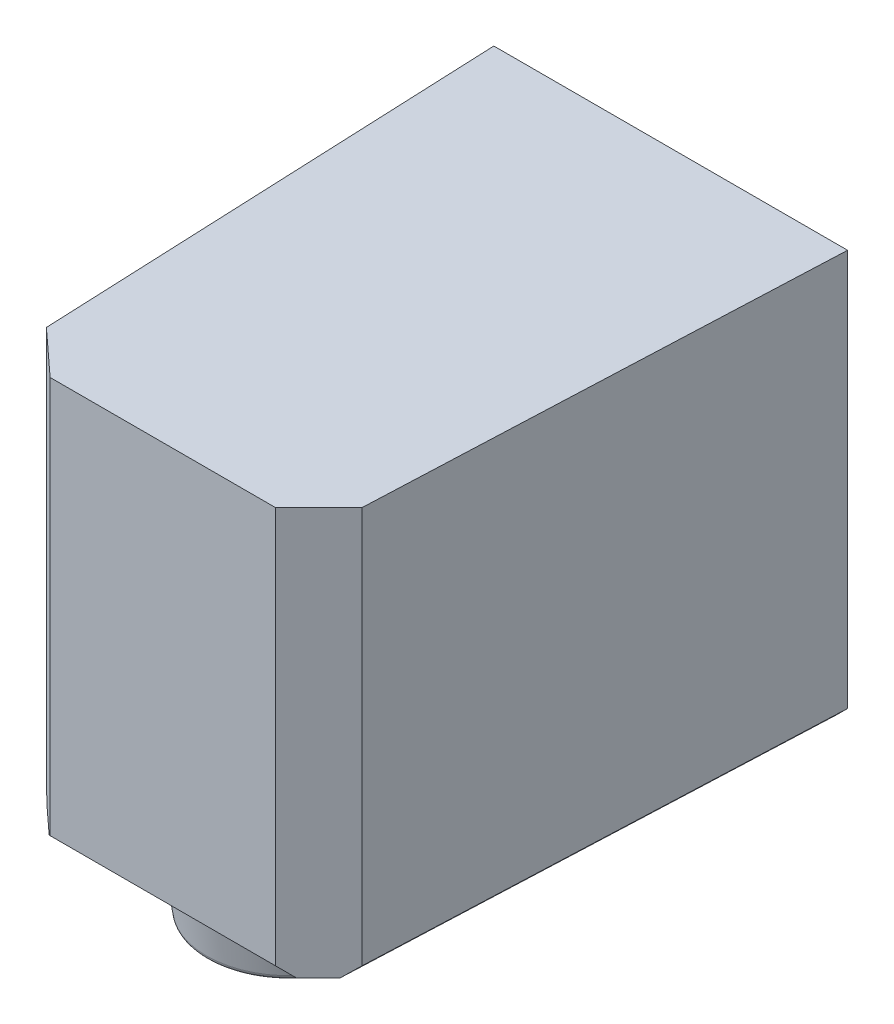
SolidWorks part; units mm, degrees
ref_plane "Front" through (0, 0, 0) normal (0, 0, 1) x (1, 0, 0)
ref_plane "Top" through (0, 0, 0) normal (0, 1, 0) x (1, 0, 0)
ref_plane "Right" through (0, 0, 0) normal (1, 0, 0) x (0, 0, -1)
sketch "Sketch1" plane through (0, 0, 0) normal (0, 1, 0) x (1, 0, 0)
  line L0 (0, 0) -> (68.2, 0)
  line L1 (68.2, 0) -> (64, -98.1)
  line L2 (64, -98.1) -> (4.2, -98.1)
  line L3 (4.2, -98.1) -> (0, 0)
  line L4 (68.2, 0) -> (68.2, -98.1) construction
  line L5 (68.2, -98.1) -> (64, -98.1) construction
  line L6 (0, 0) -> (0, -98.1) construction
  line L7 (0, -98.1) -> (4.2, -98.1) construction
  dimension "D1" = 68.2
  dimension "D2" = 59.8
  dimension "D3" = 98.1
  dimension "D4" = 87.548
extrude "Boss-Extrude1" add sketch "Sketch1" along normal blind 78.5
sketch "Sketch4" plane through (0, 0, 0) normal (0, -1, 0) x (1, 0, 0)
  line L0 (34.1, 98.1) -> (34.1, 0) construction
  line L1 (4.2, 98.1) -> (64, 98.1) construction
  line L2 (68.2, 0) -> (0, 0) construction
  circle A0 centre (34.1, 73.6) radius 17.5
  point P8 (34.1, 56.1)
  dimension "D1" = 35
  dimension "D2" = 42
extrude "Boss-Extrude2" add sketch "Sketch4" along normal blind 12.5 draft 8
fillet "Fillet1" radius 1 1 edges at (34.1, -12.5, 57.8568)
fillet "Fillet2" radius 1 1 edges at (34.1, 0, 56.1)
chamfer "Chamfer1" distance 2 angle 45 3 edges at (2.1, 0, 49.05) (34.1, 0, 98.1) (66.1, 0, 49.05)
chamfer "Chamfer2" distance 8 angle 45 2 edges at (4.2, 40.25, 98.1) (64, 40.25, 98.1)
